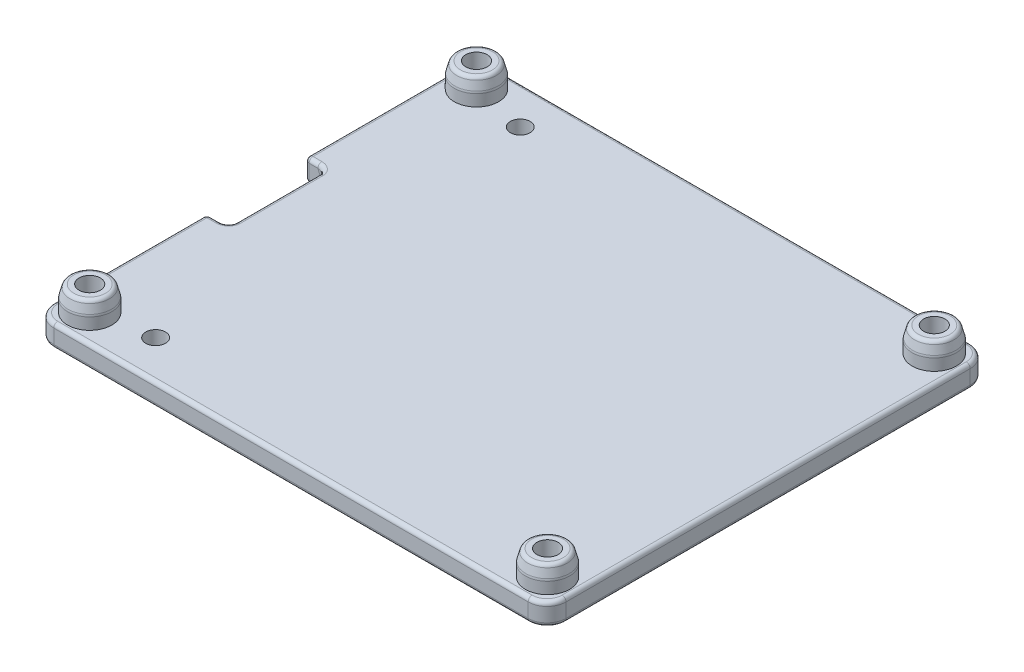
SolidWorks part; units mm, degrees
ref_plane "Front Plane" through (0, 0, 0) normal (0, 0, 1) x (1, 0, 0)
ref_plane "Top Plane" through (0, 0, 0) normal (0, 1, 0) x (1, 0, 0)
ref_plane "Right Plane" through (0, 0, 0) normal (1, 0, 0) x (0, 0, -1)
ref_plane "Plane1" through (0, -3, 0) normal (0, -1, 0) x (-1, 0, 0)
sketch "Sketch1" plane through (0, -3, 0) normal (0, -1, 0) x (-1, 0, 0)
  line L3 (42.55, -25.6) -> (42.55, 25.6) construction
  line L4 (40.05, -28.1) -> (-40.1, -28.1) construction
  line L5 (-22.55, -25.6) -> (-22.55, 25.6) construction
  line L6 (40.05, 28.1) -> (-40.1, 28.1) construction
  line L11 (42.55, -6.2) -> (40.05, -6.2) construction
  line L12 (40.05, 6.25) -> (40.05, -6.2) construction
  line L13 (42.55, 6.25) -> (40.05, 6.25) construction
  line L14 (42.55, -6.2) -> (40.05, -6.2)
  line L15 (40.05, 6.25) -> (40.05, -6.2)
  line L16 (42.55, 6.25) -> (40.05, 6.25)
  line L17 (42.55, -25.6) -> (42.55, 25.6) construction
  line L18 (40.05, -28.1) -> (-20.05, -28.1) construction
  line L19 (-22.55, -25.6) -> (-22.55, 25.6) construction
  line L20 (40.05, 28.1) -> (-20.05, 28.1) construction
  line L21 (-22.45, -25.6) -> (-22.45, 25.6)
  line L22 (40.05, -28) -> (-20.05, -28)
  line L23 (42.45, -25.6) -> (42.45, 25.6)
  line L24 (40.05, 28) -> (-20.05, 28)
  arc A4 (42.55, 25.6) -> (40.05, 28.1) centre (40.05, 25.6) ccw construction
  arc A5 (40.05, -28.1) -> (42.55, -25.6) centre (40.05, -25.6) ccw construction
  arc A6 (-22.55, -25.6) -> (-20.05, -28.1) centre (-20.05, -25.6) ccw construction
  arc A7 (-20.05, 28.1) -> (-22.55, 25.6) centre (-20.05, 25.6) ccw construction
  arc A9 (42.55, 25.6) -> (40.05, 28.1) centre (40.05, 25.6) ccw construction
  arc A10 (40.05, -28.1) -> (42.55, -25.6) centre (40.05, -25.6) ccw construction
  arc A11 (-22.55, -25.6) -> (-20.05, -28.1) centre (-20.05, -25.6) ccw construction
  circle A12 centre (39, 24.5) radius 2.8
  circle A13 centre (-19, -24.5) radius 2.8
  circle A14 centre (39, -24.5) radius 2.8
  circle A15 centre (-19, 24.5) radius 2.8
  arc A20 (40.3286, 21.8102) -> (36.3426, 25.8922) centre (39, 24.5) ccw construction
  arc A21 (-20.05, 28.1) -> (-22.55, 25.6) centre (-20.05, 25.6) ccw construction
  arc A22 (-20.05, 28) -> (-22.45, 25.6) centre (-20.05, 25.6) ccw
  arc A23 (-22.45, -25.6) -> (-20.05, -28) centre (-20.05, -25.6) ccw
  arc A24 (40.05, -28) -> (42.45, -25.6) centre (40.05, -25.6) ccw
  arc A25 (42.45, 25.6) -> (40.05, 28) centre (40.05, 25.6) ccw
  dimension "D2" = 0.2
  dimension "D1" = 0.1
extrude "Boss-Extrude1" add sketch "Sketch1" along normal up to surface (2.8 mm away) from offset 0.2 contours A24 A12 A13 A14 A15 | A15 | A12 | A14 | A13 region at (-9.7333, -3, 0.0002) region at (-39, -3, -24.5) region at (19, -3, 24.5) region at (-39, -3, 24.5) region at (19, -3, -24.5)
extrude "Boss-Extrude2" add sketch "Sketch1<4>" against normal offset from surface (5.9 mm away) 0.2 from surface contours A15 | A12 | A14 | A13 region at (-39, -3, -24.5) region at (19, -3, 24.5) region at (-39, -3, 24.5) region at (19, -3, -24.5) starting at face at (-20.4167, -6, -0.0083)
sketch "Sketch1<4>" plane through (0, -3, 0) normal (0, -1, 0) x (-1, 0, 0) same geometry as "Sketch1"
chamfer "Chamfer2" distance 3 angle 22.5 1 edges at (-40.05, -6, -0.025) first distance on face at (-40.05, -4.6, -0.025)
sketch "Sketch2" plane through (0, -6, 0) normal (0, -1, 0) x (1, 0, 0)
  line L8 (-38.8074, -6.25) -> (-42.45, -6.25)
  line L9 (-38.8074, -6.25) -> (-42.45, -6.25)
  line L10 (-42.45, 6.2) -> (-38.8074, 6.2)
  line L11 (-42.45, 6.2) -> (-38.8074, 6.2)
  line L12 (-38.8074, 6.2) -> (-38.8074, -6.25)
  line L13 (-38.8074, 6.2) -> (-38.8074, -6.25)
  line L14 (-42.45, -6.25) -> (-42.45, -25.6)
  line L28 (-42.45, -6.25) -> (-42.45, -25.6)
  line L30 (-40.05, -28) -> (20.05, -28)
  line L32 (-40.05, -28) -> (20.05, -28)
  line L34 (22.45, -25.6) -> (22.45, 25.6)
  line L36 (22.45, -25.6) -> (22.45, 25.6)
  line L37 (20.05, 28) -> (-40.05, 28)
  line L38 (20.05, 28) -> (-40.05, 28)
  line L39 (-42.45, 25.6) -> (-42.45, 6.2)
  line L40 (-42.45, 25.6) -> (-42.45, 6.2)
  circle A0 centre (-32.05, -23.1) radius 1.25 construction
  circle A1 centre (-32.05, -23.1) radius 3.5 construction
  circle A2 centre (-32.05, 23.1) radius 3.5 construction
  circle A3 centre (-32.05, 23.1) radius 1.25 construction
  arc A4 (-40.05, 28) -> (-42.45, 25.6) centre (-40.05, 25.6) ccw
  arc A5 (-40.05, 28) -> (-42.45, 25.6) centre (-40.05, 25.6) ccw
  arc A6 (-42.45, -25.6) -> (-40.05, -28) centre (-40.05, -25.6) ccw
  circle A12 centre (-32.05, -23.1) radius 1.25
  circle A13 centre (-32.05, -23.1) radius 3.5
  circle A14 centre (-32.05, 23.1) radius 3.5
  circle A15 centre (-32.05, 23.1) radius 1.25
  arc A20 (-42.45, -25.6) -> (-40.05, -28) centre (-40.05, -25.6) ccw
  arc A22 (20.05, -28) -> (22.45, -25.6) centre (20.05, -25.6) ccw
  arc A24 (20.05, -28) -> (22.45, -25.6) centre (20.05, -25.6) ccw
  arc A25 (22.45, 25.6) -> (20.05, 28) centre (20.05, 25.6) ccw
  arc A26 (22.45, 25.6) -> (20.05, 28) centre (20.05, 25.6) ccw
  dimension "D1" = 0
extrude "Cut-Extrude1" cut sketch "Sketch2" against normal blind 1 contours A14 A15 | A13 A12 region at (-35.451, -6, -23.1) region at (-35.451, -6, 23.1)
extrude "Cut-Extrude2" cut sketch "Sketch2<3>" against normal up to next contours A15 | A12 region at (-32.05, -6, -23.1) region at (-32.05, -6, 23.1)
sketch "Sketch2<3>" plane through (0, -6, 0) normal (0, -1, 0) x (1, 0, 0) same geometry as "Sketch2"
sketch "Sketch3" plane through (0, -6, 0) normal (0, -1, 0) x (1, 0, 0)
  line L8 (-38.8074, -6.25) -> (-42.45, -6.25)
  line L9 (-38.8074, -6.25) -> (-42.45, -6.25)
  line L10 (-42.45, 6.2) -> (-38.8074, 6.2)
  line L11 (-42.45, 6.2) -> (-38.8074, 6.2)
  line L12 (-38.8074, 6.2) -> (-38.8074, -6.25)
  line L13 (-38.8074, 6.2) -> (-38.8074, -6.25)
  line L14 (-42.45, -6.25) -> (-42.45, -25.6)
  line L76 (-42.45, -6.25) -> (-42.45, -25.6)
  line L78 (-40.05, -28) -> (20.05, -28)
  line L80 (-40.05, -28) -> (20.05, -28)
  line L82 (22.45, -25.6) -> (22.45, 25.6)
  line L84 (22.45, -25.6) -> (22.45, 25.6)
  line L85 (20.05, 28) -> (-40.05, 28)
  line L86 (20.05, 28) -> (-40.05, 28)
  line L87 (-42.45, 25.6) -> (-42.45, 6.2)
  line L88 (-42.45, 25.6) -> (-42.45, 6.2)
  circle A0 centre (-39, 24.5) radius 1.35
  circle A1 centre (-39, 24.5) radius 2.4
  circle A2 centre (-39, -24.5) radius 1.35
  circle A3 centre (19, 24.5) radius 1.35
  arc A4 (-40.05, 28) -> (-42.45, 25.6) centre (-40.05, 25.6) ccw
  arc A5 (-40.05, 28) -> (-42.45, 25.6) centre (-40.05, 25.6) ccw
  arc A6 (-42.45, -25.6) -> (-40.05, -28) centre (-40.05, -25.6) ccw
  circle A12 centre (19, -24.5) radius 1.35
  circle A13 centre (19, 24.5) radius 2.4
  circle A14 centre (19, -24.5) radius 2.4
  circle A15 centre (-39, -24.5) radius 2.4
  arc A20 (-42.45, -25.6) -> (-40.05, -28) centre (-40.05, -25.6) ccw
  arc A22 (20.05, -28) -> (22.45, -25.6) centre (20.05, -25.6) ccw
  arc A24 (20.05, -28) -> (22.45, -25.6) centre (20.05, -25.6) ccw
  arc A25 (22.45, 25.6) -> (20.05, 28) centre (20.05, 25.6) ccw
  arc A26 (22.45, 25.6) -> (20.05, 28) centre (20.05, 25.6) ccw
  dimension "D2" = 4.8
  dimension "D3" = 2.7
  dimension "D1" = 0
extrude "Cut-Extrude3" cut sketch "Sketch3" against normal blind 2 contours A1 A0 | A13 A3 | A14 A12 | A15 A2 region at (-41.3321, -6, 24.5) region at (16.6679, -6, 24.5) region at (16.6679, -6, -24.5) region at (-41.3321, -6, -24.5)
extrude "Cut-Extrude4" cut sketch "Sketch3<3>" against normal through all both and the other way through all contours A0 | A3 | A12 | A2 region at (-39, -6, 24.5) region at (-39, -6, -24.5) region at (19, -6, 24.5) region at (19, -6, -24.5)
sketch "Sketch3<3>" plane through (0, -6, 0) normal (0, -1, 0) x (1, 0, 0) same geometry as "Sketch3"
chamfer "Chamfer3" distance 1.5 angle 15 4 edges at (19, -0.1, 27.3) (19, -0.1, -21.7) (-39, -0.1, 27.3) (-39, -0.1, -21.7) first distance on face at (19, -0.1, 27.3) first distance on face at (19, -0.1, -21.7) first distance on face at (-39, -0.1, 27.3) first distance on face at (-39, -0.1, -21.7)
fillet "Fillet2" radius 1 6 edges at (-39.3873, -4.6, 6.2) (-39.3873, -4.6, -6.25) (-39, -1.6, 27.3) (19, -1.6, 27.3) (19, -1.6, -21.7) (-39, -1.6, -21.7)
fillet "Fillet1" radius 0.5 42 edges at (-41.7471, -6, 27.2971) (-41.1699, -6, 6.2) (-39.1244, -6, 5.9071) (-41.1699, -6, -6.25) (-39.1244, -6, -5.9571) (-38.8074, -6, -0.025) (-41.7471, -3.2, 27.2971) (-41.7498, -3.2, -6.25) (-40.2842, -3.2, -5.9571) (-41.7498, -3.2, 6.2) (-40.2842, -3.2, 5.9071) (-39.9672, -3.2, -0.025) (19, -4, -26.9) (19, -4, 22.1) (-39, -4, 22.1) (-39, -4, -26.9) (-39, -6, -26.9) (-39, -6, 22.1) (19, -6, 22.1) (19, -6, -26.9) (-42.45, -3.2, 15.9) (-10, -3.2, 28) (21.7471, -3.2, 27.2971) (-42.45, -3.2, -15.925) (-41.7471, -3.2, -27.2971) (-10, -3.2, -28) (21.7471, -3.2, -27.2971) (-42.45, -6, -15.925) (-41.7471, -6, -27.2971) (-10, -6, -28) (21.7471, -6, -27.2971) (-42.45, -6, 15.9) (-10, -6, 28) (21.7471, -6, 27.2971) (22.45, -3.2, 0) (22.45, -6, 0) (-42.45, -4.6, -6.25) (-42.45, -4.6, 6.2) (19, -0.1, -22.1019) (19, -0.1, 26.8981) (-39, -0.1, -22.1019) (-39, -0.1, 26.8981)
